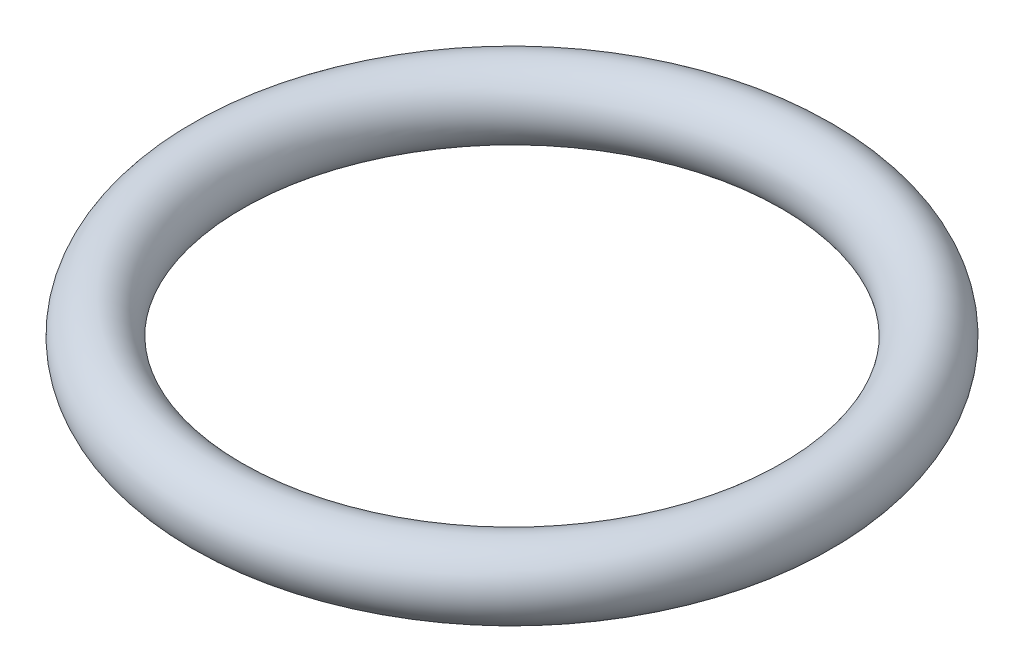
SolidWorks part; units mm, degrees
note: '?' marks a value the reader was unsure of.
ref_plane "Ebene vorne" through (0, 0, 0) normal (0, 0, 1) x (1, 0, 0)
ref_plane "Ebene oben" through (0, 0, 0) normal (0, 1, 0) x (1, 0, 0)
ref_plane "Ebene rechts" through (0, 0, 0) normal (1, 0, 0) x (0, 0, -1)
sketch "Skizze1" plane through (0, 0, 0) normal (0, 0, 1) x (1, 0, 0)
  line L0 (0, 0) -> (0, 316.43)
  circle A0 centre (-442.5, 0) radius 42.5
  point P5 (0, 316.43)
  dimension "D1" = 85
  dimension "D2" = 442.5
revolve "Rotation-Dünn1" add sketch "Skizze1" angle 360 about L0
ref_axis "Achse1" through (0, 0, 0) along (0, 1, 0)?
ref_axis "Achse2" through (-544.5, 0, 0) along (1, 0, 0)?
ref_axis "Achse3" through (0, 0, -544.5) along (0, 0, 1)?
